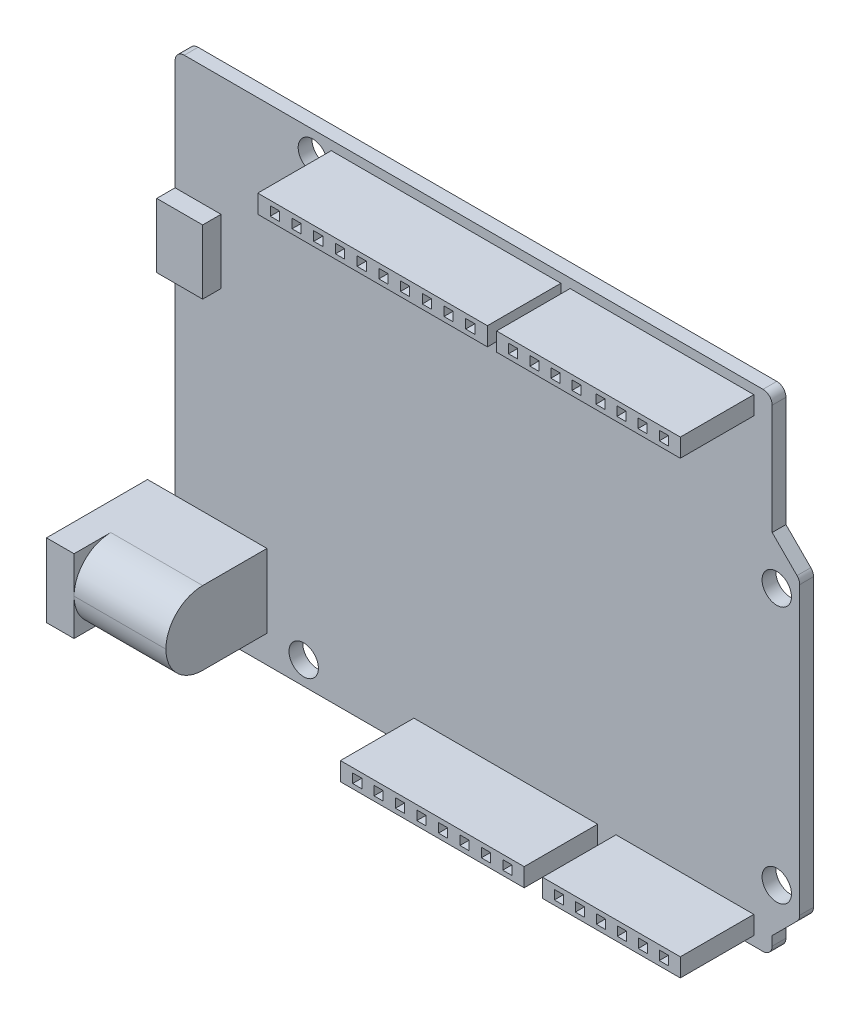
SolidWorks part; units mm, degrees
ref_plane "Plan de face" through (0, 0, 0) normal (0, 0, 1) x (1, 0, 0)
ref_plane "Plan de dessus" through (0, 0, 0) normal (0, 1, 0) x (1, 0, 0)
ref_plane "Plan de droite" through (0, 0, 0) normal (1, 0, 0) x (0, 0, -1)
sketch "Esquisse1" plane through (0, 0, 0) normal (0, 0, 1) x (1, 0, 0)
  line L0 (0, 0) -> (0, 53)
  line L1 (0, 53) -> (65, 53)
  line L2 (65, 53) -> (65, 40)
  line L3 (65, 40) -> (68, 37)
  line L4 (68, 37) -> (68, 5)
  line L5 (68, 5) -> (65, 2)
  line L6 (65, 2) -> (65, 0)
  line L7 (65, 0) -> (0, 0)
  dimension "D1" = 53
  dimension "D2" = 65
  dimension "D3" = 13
  dimension "D4" = 3
  dimension "D5" = 3
  dimension "D6" = 32
  dimension "D7" = 3
  dimension "D8" = 3
  dimension "D9" = 2
extrude "Boss.-Extru.1" add sketch "Esquisse1" along normal blind 1.5
sketch "Esquisse2" plane through (0, 0, 1.5) normal (0, 0, 1) x (1, 0, 0)
  line L0 (0, 53) -> (15, 53) construction
  line L1 (65, 53) -> (0, 53) construction
  line L2 (0, 0) -> (0, 50.5) construction
  line L3 (0, 53) -> (0, 0) construction
  line L4 (0, 50.5) -> (15, 50.5) construction
  line L5 (65, 0) -> (65.5, 0) construction
  line L6 (65.5, 0) -> (65.5, 7) construction
  line L7 (65.5, 7) -> (65.5, 34.9893) construction
  line L8 (0, 0) -> (0, 2.5) construction
  line L9 (0, 2.5) -> (14, 2.5) construction
  circle A0 centre (15, 50.5) radius 1.6
  circle A1 centre (65.5, 7) radius 1.6
  circle A2 centre (65.5, 34.9893) radius 1.6
  circle A3 centre (14, 2.5) radius 1.6
  dimension "D4" = 3.2
  dimension "D7" = 3.2
  dimension "D8" = 3.2
  dimension "D11" = 3.2
  dimension "D1" = 15
  dimension "D2" = 50.5
  dimension "D3" = 2.5
  dimension "D5" = 0.5
  dimension "D6" = 7
  dimension "D9" = 2.5
  dimension "D10" = 14
extrude "Enlèv. mat.-Extru.1" cut sketch "Esquisse2" against normal blind 2
sketch "Esquisse5" plane through (0, 0, 1.5) normal (0, 0, 1) x (1, 0, 0)
sketch "Esquisse6" plane through (0, 0, 1.5) normal (0, 0, 1) x (1, 0, 0)
  line L0 (0, 0) -> (0, 3) construction
  line L1 (0, 53) -> (0, 0) construction
  line L2 (0, 3) -> (0, 11)
  line L3 (0, 11) -> (10, 11)
  line L4 (0, 3) -> (10, 3)
  line L5 (10, 3) -> (10, 11)
  dimension "D1" = 3
  dimension "D2" = 8
  dimension "D3" = 10
extrude "Boss.-Extru.2" add sketch "Esquisse6" along normal blind 11
fillet "Congé1" radius 4 2 edges at (5, 11, 12.5) (5, 3, 12.5)
sketch "Esquisse7" plane through (0, 0, 0) normal (-1, 0, 0) x (0, 0, 1)
  line L0 (1.5, 11) -> (1.5, 3)
  line L1 (1.5, 3) -> (12.5, 3)
  line L2 (12.5, 3) -> (12.5, 11)
  line L3 (12.5, 11) -> (1.5, 11)
  dimension "D1" = 11
extrude "Boss.-Extru.3" add sketch "Esquisse7" along normal blind 3
sketch "Esquisse8" plane through (-3, 0, 0) normal (-1, 0, 0) x (0, 0, 1)
  line L0 (1.5, 7) -> (7.5, 7) construction
  line L2 (1.5, 11) -> (1.5, 3) construction
  circle A0 centre (7.5, 7) radius 3
  dimension "D2" = 6
  dimension "D1" = 6
extrude "Enlèv. mat.-Extru.2" cut sketch "Esquisse8" against normal blind 10
sketch "Esquisse9" plane through (7, 0, 0) normal (-1, 0, 0) x (0, 0, 1)
  circle A0 centre (7.5, 7) radius 1
  dimension "D1" = 2
extrude "Boss.-Extru.4" add sketch "Esquisse9" along normal blind 8
fillet "Congé3" radius 0.4 1 edges at (-1, 7, 8.5)
sketch "Esquisse10" plane through (0, 0, 1.5) normal (0, 0, 1) x (1, 0, 0)
  line L0 (0, 11) -> (0, 33) construction
  line L1 (0, 53) -> (0, 11) construction
  line L2 (0, 33) -> (5, 33)
  line L3 (5, 33) -> (5, 40)
  line L4 (5, 40) -> (0, 40)
  line L5 (0, 40) -> (0, 33)
  dimension "D1" = 22
  dimension "D2" = 5
  dimension "D3" = 7
extrude "Boss.-Extru.5" add sketch "Esquisse10" along normal blind 2
sketch "Esquisse11" plane through (0, 0, 0) normal (-1, 0, 0) x (0, 0, 1)
  line L0 (1.5, 40) -> (1.5, 33) construction
  line L1 (1.5, 40) -> (1.5, 39.9) construction
  line L2 (1.5, 39.9) -> (3.5, 39.9) construction
  line L3 (3.5, 40) -> (3.5, 33) construction
  line L4 (3.5, 39.9) -> (3.4, 39.9) construction
  line L5 (3.4, 40) -> (3.4, 33) construction
  line L6 (3.5, 40) -> (1.5, 40) construction
  line L7 (3.5, 33) -> (1.5, 33) construction
  line L8 (3.4, 33) -> (3.4, 33.1) construction
  line L9 (3.4, 33.1) -> (1.5, 33.1) construction
  line L10 (1.5, 39.9) -> (1.6, 39.9) construction
  line L11 (1.6, 39.9) -> (1.6, 33.1) construction
  line L12 (1.6, 39.9) -> (3.4, 39.9)
  line L13 (3.4, 39.9) -> (3.4, 33.1)
  line L14 (3.4, 33.1) -> (1.6, 33.1)
  line L15 (1.6, 33.1) -> (1.6, 39.9)
  dimension "D1" = 0.1
  dimension "D2" = 0.1
  dimension "D3" = 0.1
  dimension "D4" = 0.1
extrude "Enlèv. mat.-Extru.3" cut sketch "Esquisse11" against normal blind 4
sketch "Esquisse14" plane through (4, 0, 0) normal (-1, 0, 0) x (0, 0, 1)
  line L0 (1.6, 36.5) -> (2.6, 36.5) construction
  line L2 (1.6, 39.9) -> (1.6, 33.1) construction
  line L3 (2.6, 35) -> (2.6, 38)
  line L4 (2.6, 36.5) -> (2.9, 36.5) construction
  line L5 (2.9, 36.5) -> (3.4, 36.5) construction
  line L6 (3.4, 33.1) -> (3.4, 39.9) construction
  line L7 (2.9, 35) -> (2.9, 38)
  line L8 (2.9, 38) -> (2.6, 38)
  line L9 (2.9, 35) -> (2.6, 35)
  dimension "D1" = 1
  dimension "D2" = 1.5
  dimension "D3" = 0.3
extrude "Boss.-Extru.6" add sketch "Esquisse14" along normal blind 3.5
sketch "Esquisse15" plane through (0, 0, 1.5) normal (0, 0, 1) x (1, 0, 0)
  line L0 (0, 0) -> (0, 1) construction
  line L1 (0, 3) -> (0, 0) construction
  line L2 (0, 1) -> (26, 1) construction
  line L3 (26, 1) -> (26, 3)
  line L4 (26, 1) -> (46, 1)
  line L5 (26, 3) -> (46, 3)
  line L6 (46, 3) -> (46, 1)
  line L7 (46, 1) -> (48, 1) construction
  line L8 (48, 1) -> (48, 3)
  line L9 (48, 3) -> (63, 3)
  line L10 (48, 1) -> (63, 1)
  line L11 (63, 1) -> (63, 3)
  line L13 (0, 53) -> (0, 52) construction
  line L14 (0, 53) -> (0, 40) construction
  line L15 (0, 52) -> (17, 52) construction
  line L16 (17, 52) -> (17, 50)
  line L17 (17, 52) -> (42, 52)
  line L18 (17, 50) -> (42, 50)
  line L19 (42, 50) -> (42, 52)
  line L20 (42, 52) -> (43, 52) construction
  line L21 (43, 52) -> (43, 50)
  line L22 (43, 50) -> (63, 50)
  line L23 (63, 50) -> (63, 52)
  line L24 (63, 52) -> (43, 52)
  dimension "D1" = 1
  dimension "D2" = 26
  dimension "D3" = 2
  dimension "D4" = 20
  dimension "D5" = 2
  dimension "D6" = 15
  dimension "D7" = 2
  dimension "D8" = 1
  dimension "D9" = 17
  dimension "D10" = 2
  dimension "D11" = 25
  dimension "D12" = 1
  dimension "D13" = 20
  dimension "D14" = 2
extrude "Boss.-Extru.7" add sketch "Esquisse15" along normal blind 8
sketch "Esquisse17" plane through (0, 0, 9.5) normal (0, 0, 1) x (1, 0, 0)
  line L0 (36, 1) -> (36, 3) construction
  line L1 (26, 1) -> (46, 1) construction
  line L2 (46, 3) -> (26, 3) construction
  line L3 (26, 1) -> (26, 1.5) construction
  line L4 (26, 3) -> (26, 1) construction
  line L5 (26, 1.5) -> (27.33, 1.5) construction
  line L6 (27.33, 1.5) -> (28.33, 1.5)
  line L7 (28.33, 1.5) -> (29.66, 1.5) construction
  line L8 (29.66, 1.5) -> (30.66, 1.5)
  line L9 (30.66, 1.5) -> (31.99, 1.5) construction
  line L10 (31.99, 1.5) -> (32.99, 1.5)
  line L11 (32.99, 1.5) -> (34.32, 1.5) construction
  line L12 (34.32, 1.5) -> (35.32, 1.5)
  line L13 (27.33, 1.5) -> (27.33, 2.5)
  line L14 (28.33, 1.5) -> (28.33, 2.5)
  line L15 (28.33, 2.5) -> (27.33, 2.5)
  line L16 (29.66, 1.5) -> (29.66, 2.5)
  line L17 (29.66, 2.5) -> (30.66, 2.5)
  line L18 (30.66, 2.5) -> (30.66, 1.5)
  line L19 (31.99, 1.5) -> (31.99, 2.5)
  line L20 (31.99, 2.5) -> (32.99, 2.5)
  line L21 (32.99, 2.5) -> (32.99, 1.5)
  line L22 (34.32, 1.5) -> (34.32, 2.5)
  line L23 (34.32, 2.5) -> (35.32, 2.5)
  line L24 (35.32, 2.5) -> (35.32, 1.5)
  line L25 (37.68, 1.5) -> (36.68, 1.5)
  line L26 (36.68, 2.5) -> (36.68, 1.5)
  line L27 (37.68, 1.5) -> (37.68, 2.5)
  line L28 (37.68, 2.5) -> (36.68, 2.5)
  line L29 (39.01, 2.5) -> (39.01, 1.5)
  line L30 (40.01, 1.5) -> (39.01, 1.5)
  line L31 (40.01, 1.5) -> (40.01, 2.5)
  line L32 (40.01, 2.5) -> (39.01, 2.5)
  line L33 (41.34, 2.5) -> (41.34, 1.5)
  line L34 (42.34, 1.5) -> (41.34, 1.5)
  line L35 (42.34, 2.5) -> (41.34, 2.5)
  line L36 (42.34, 1.5) -> (42.34, 2.5)
  line L37 (43.67, 1.5) -> (43.67, 2.5)
  line L38 (44.67, 1.5) -> (43.67, 1.5)
  line L39 (43.67, 2.5) -> (44.67, 2.5)
  line L40 (44.67, 1.5) -> (44.67, 2.5)
  line L41 (48, 1) -> (48, 1.5) construction
  line L42 (48, 3) -> (48, 1) construction
  line L43 (55.5, 1) -> (55.5, 3) construction
  line L44 (48, 1) -> (63, 1) construction
  line L45 (63, 3) -> (48, 3) construction
  line L46 (48, 1.5) -> (49.286, 1.5) construction
  line L47 (49.286, 1.5) -> (50.286, 1.5)
  line L48 (50.286, 1.5) -> (51.572, 1.5) construction
  line L49 (51.572, 1.5) -> (52.572, 1.5)
  line L50 (52.572, 1.5) -> (53.858, 1.5) construction
  line L51 (53.858, 1.5) -> (54.858, 1.5)
  line L52 (49.286, 1.5) -> (49.286, 2.5)
  line L53 (49.286, 2.5) -> (50.286, 2.5)
  line L54 (50.286, 2.5) -> (50.286, 1.5)
  line L55 (51.572, 1.5) -> (51.572, 2.5)
  line L56 (51.572, 2.5) -> (52.572, 2.5)
  line L57 (52.572, 2.5) -> (52.572, 1.5)
  line L58 (53.858, 1.5) -> (53.858, 2.5)
  line L59 (53.858, 2.5) -> (54.858, 2.5)
  line L60 (54.858, 2.5) -> (54.858, 1.5)
  line L61 (56.142, 2.5) -> (56.142, 1.5)
  line L62 (57.142, 1.5) -> (56.142, 1.5)
  line L63 (57.142, 2.5) -> (56.142, 2.5)
  line L64 (57.142, 1.5) -> (57.142, 2.5)
  line L65 (58.428, 2.5) -> (58.428, 1.5)
  line L66 (59.428, 1.5) -> (58.428, 1.5)
  line L67 (59.428, 1.5) -> (59.428, 2.5)
  line L68 (59.428, 2.5) -> (58.428, 2.5)
  line L69 (60.714, 2.5) -> (60.714, 1.5)
  line L70 (61.714, 1.5) -> (60.714, 1.5)
  line L71 (61.714, 1.5) -> (61.714, 2.5)
  line L72 (61.714, 2.5) -> (60.714, 2.5)
  line L73 (29.5, 50) -> (29.5, 52) construction
  line L74 (17, 50) -> (42, 50) construction
  line L75 (42, 52) -> (17, 52) construction
  line L76 (17, 50) -> (17, 50.5) construction
  line L77 (17, 52) -> (17, 50) construction
  line L78 (17, 50.5) -> (18.364, 50.5) construction
  line L79 (18.364, 50.5) -> (19.364, 50.5)
  line L80 (19.364, 50.5) -> (20.728, 50.5) construction
  line L81 (20.728, 50.5) -> (21.728, 50.5)
  line L82 (21.728, 50.5) -> (23.092, 50.5) construction
  line L83 (23.092, 50.5) -> (24.092, 50.5)
  line L84 (24.092, 50.5) -> (25.456, 50.5) construction
  line L85 (25.456, 50.5) -> (26.456, 50.5)
  line L86 (26.456, 50.5) -> (27.82, 50.5) construction
  line L87 (27.82, 50.5) -> (28.82, 50.5)
  line L88 (18.364, 50.5) -> (18.364, 51.5)
  line L89 (19.364, 50.5) -> (19.364, 51.5)
  line L90 (19.364, 51.5) -> (18.364, 51.5)
  line L91 (20.728, 50.5) -> (20.728, 51.5)
  line L92 (20.728, 51.5) -> (21.728, 51.5)
  line L93 (21.728, 51.5) -> (21.728, 50.5)
  line L94 (23.092, 50.5) -> (23.092, 51.5)
  line L95 (23.092, 51.5) -> (24.092, 51.5)
  line L96 (24.092, 51.5) -> (24.092, 50.5)
  line L97 (25.456, 50.5) -> (25.456, 51.5)
  line L98 (25.456, 51.5) -> (26.456, 51.5)
  line L99 (26.456, 51.5) -> (26.456, 50.5)
  line L100 (27.82, 50.5) -> (27.82, 51.5)
  line L101 (27.82, 51.5) -> (28.82, 51.5)
  line L102 (28.82, 51.5) -> (28.82, 50.5)
  line L103 (30.18, 51.5) -> (30.18, 50.5)
  line L104 (31.18, 50.5) -> (30.18, 50.5)
  line L105 (31.18, 50.5) -> (31.18, 51.5)
  line L106 (31.18, 51.5) -> (30.18, 51.5)
  line L107 (32.544, 51.5) -> (32.544, 50.5)
  line L108 (33.544, 50.5) -> (32.544, 50.5)
  line L109 (33.544, 50.5) -> (33.544, 51.5)
  line L110 (33.544, 51.5) -> (32.544, 51.5)
  line L111 (34.908, 51.5) -> (34.908, 50.5)
  line L112 (35.908, 50.5) -> (34.908, 50.5)
  line L113 (35.908, 50.5) -> (35.908, 51.5)
  line L114 (35.908, 51.5) -> (34.908, 51.5)
  line L115 (37.272, 51.5) -> (37.272, 50.5)
  line L116 (38.272, 50.5) -> (37.272, 50.5)
  line L117 (38.272, 50.5) -> (38.272, 51.5)
  line L118 (38.272, 51.5) -> (37.272, 51.5)
  line L119 (39.636, 50.5) -> (39.636, 51.5)
  line L120 (40.636, 50.5) -> (39.636, 50.5)
  line L121 (40.636, 50.5) -> (40.636, 51.5)
  line L122 (39.636, 51.5) -> (40.636, 51.5)
  line L123 (43, 50) -> (43, 50.5) construction
  line L124 (43, 52) -> (43, 50) construction
  line L125 (43, 50.5) -> (44.3014, 50.5) construction
  line L126 (44.3014, 50.5) -> (45.2879, 50.5)
  line L127 (45.2879, 50.5) -> (46.633, 50.5) construction
  line L128 (46.633, 50.5) -> (47.6015, 50.5)
  line L129 (47.6015, 50.5) -> (48.9108, 50.5) construction
  line L130 (48.9108, 50.5) -> (49.8973, 50.5)
  line L131 (49.8973, 50.5) -> (51.2065, 50.5) construction
  line L132 (51.2065, 50.5) -> (52.193, 50.5)
  line L133 (53, 50) -> (53, 52) construction
  line L134 (43, 50) -> (63, 50) construction
  line L135 (63, 52) -> (43, 52) construction
  line L136 (44.3014, 50.5) -> (44.3014, 51.5)
  line L137 (44.3014, 51.5) -> (45.2879, 51.5)
  line L138 (45.2879, 51.5) -> (45.2879, 50.5)
  line L139 (46.633, 50.5) -> (46.633, 51.5)
  line L140 (46.633, 51.5) -> (47.6015, 51.5)
  line L141 (47.6015, 51.5) -> (47.6015, 50.5)
  line L142 (48.9108, 50.5) -> (48.9108, 51.5)
  line L143 (48.9108, 51.5) -> (49.8973, 51.5)
  line L144 (49.8973, 51.5) -> (49.8973, 50.5)
  line L145 (51.2065, 50.5) -> (51.2065, 51.5)
  line L146 (51.2065, 51.5) -> (52.193, 51.5)
  line L147 (52.193, 51.5) -> (52.193, 50.5)
  line L148 (53.807, 51.5) -> (53.807, 50.5)
  line L149 (54.7935, 50.5) -> (53.807, 50.5)
  line L150 (54.7935, 50.5) -> (54.7935, 51.5)
  line L151 (54.7935, 51.5) -> (53.807, 51.5)
  line L152 (56.1027, 51.5) -> (56.1027, 50.5)
  line L153 (57.0892, 50.5) -> (56.1027, 50.5)
  line L154 (57.0892, 50.5) -> (57.0892, 51.5)
  line L155 (57.0892, 51.5) -> (56.1027, 51.5)
  line L156 (58.3985, 51.5) -> (58.3985, 50.5)
  line L157 (59.367, 50.5) -> (58.3985, 50.5)
  line L158 (59.367, 50.5) -> (59.367, 51.5)
  line L159 (59.367, 51.5) -> (58.3985, 51.5)
  line L160 (60.7121, 51.5) -> (60.7121, 50.5)
  line L161 (61.6986, 50.5) -> (60.7121, 50.5)
  line L162 (61.6986, 51.5) -> (60.7121, 51.5)
  line L163 (61.6986, 50.5) -> (61.6986, 51.5)
  dimension "D1" = 0.5
  dimension "D2" = 1.33
  dimension "D3" = 1
  dimension "D4" = 1.33
  dimension "D5" = 1
  dimension "D6" = 1.33
  dimension "D7" = 1
  dimension "D8" = 1.33
  dimension "D9" = 1
  dimension "D10" = 1
  dimension "D11" = 1.286
  dimension "D12" = 1
  dimension "D13" = 1.286
  dimension "D14" = 1
  dimension "D15" = 1.286
  dimension "D16" = 1
  dimension "D17" = 0.5
  dimension "D18" = 1.364
  dimension "D19" = 1
  dimension "D20" = 1.364
  dimension "D21" = 1
  dimension "D22" = 1.364
  dimension "D23" = 1
  dimension "D24" = 1.364
  dimension "D25" = 1
  dimension "D26" = 1.364
  dimension "D27" = 1
  dimension "D28" = 1
extrude "Enlèv. mat.-Extru.4" cut sketch "Esquisse17" against normal blind 5
fillet "Congé4" radius 1 6 edges at (0, 0, 0.75) (65, 0, 0.75) (68, 5, 0.75) (68, 37, 0.75) (65, 53, 0.75) (0, 53, 0.75)
